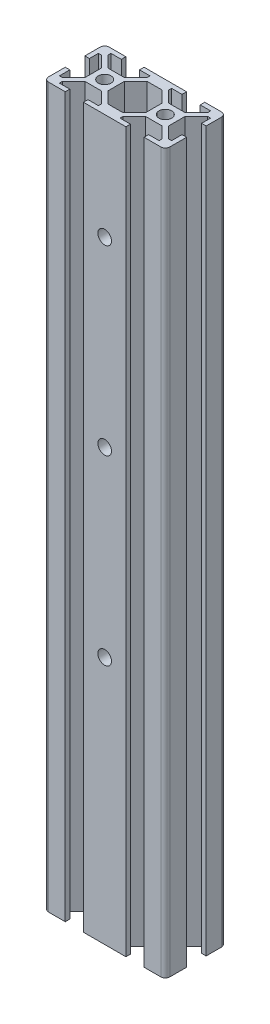
SolidWorks part; units mm, degrees
material "6063-O, Extruded Rod (SS)"
ref_plane "Front Plane" through (0, 0, 0) normal (0, 0, 1) x (1, 0, 0)
ref_plane "Top Plane" through (0, 0, 0) normal (0, 1, 0) x (1, 0, 0)
ref_plane "Right Plane" through (0, 0, 0) normal (1, 0, 0) x (0, 0, -1)
sketch "Sketch1" plane through (0, 0, 0) normal (0, 1, 0) x (1, 0, 0)
  line L0 (0, 0) -> (7, 0)
  line L1 (0, 0) -> (40, 0) construction
  line L2 (0, 0) -> (0, 20) construction
  line L3 (0, 20) -> (40, 20) construction
  line L4 (40, 0) -> (40, 20) construction
  line L5 (7, 0) -> (7, 1.5)
  line L6 (7, 1.5) -> (3.5607, 1.5)
  line L7 (3.5607, 1.5) -> (3.5607, 2.5)
  line L8 (3.5607, 2.5) -> (7.2607, 6.2)
  line L9 (12.7393, 6.2) -> (16.4393, 2.5)
  line L10 (16.4393, 2.5) -> (16.4393, 1.5)
  line L11 (13, 1.5) -> (13, 0)
  line L12 (13, 0) -> (27, 0)
  line L13 (27, 0) -> (27, 1.5)
  line L14 (27, 1.5) -> (23.5607, 1.5)
  line L15 (23.5607, 1.5) -> (23.5607, 2.5)
  line L16 (23.5607, 2.5) -> (27.2607, 6.2)
  line L17 (36.4393, 2.5) -> (36.4393, 1.5)
  line L18 (36.4393, 1.5) -> (33, 1.5)
  line L19 (33, 1.5) -> (33, 0)
  line L20 (33, 0) -> (40, 0)
  line L21 (40, 0) -> (40, 7)
  line L22 (40, 7) -> (38.5, 7)
  line L23 (38.5, 7) -> (38.5, 3.5607)
  line L24 (38.5, 3.5607) -> (37.5, 3.5607)
  line L25 (37.5, 3.5607) -> (33.8, 7.2607)
  line L26 (33.8, 7.2607) -> (33.8, 12.7393)
  line L27 (33.8, 12.7393) -> (37.5, 16.4393)
  line L28 (37.5, 16.4393) -> (38.5, 16.4393)
  line L29 (38.5, 16.4393) -> (38.5, 13.4532)
  line L30 (38.5, 13.4532) -> (40, 13.4532)
  line L31 (40, 13.4532) -> (40, 20)
  line L32 (40, 20) -> (33, 20)
  line L33 (33, 20) -> (33, 18.5)
  line L34 (33, 18.5) -> (36.4393, 18.5)
  line L35 (36.4393, 18.5) -> (36.4393, 17.5)
  line L36 (36.4393, 17.5) -> (32.7393, 13.8)
  line L37 (32.7393, 13.8) -> (27.2607, 13.8)
  line L38 (27.2607, 13.8) -> (23.5607, 17.5)
  line L39 (23.5607, 17.5) -> (23.5607, 18.5)
  line L40 (23.5607, 18.5) -> (27, 18.5)
  line L41 (27, 18.5) -> (27, 20)
  line L42 (27, 20) -> (13, 20)
  line L43 (13, 20) -> (13, 18.5)
  line L44 (13, 18.5) -> (16.4393, 18.5)
  line L45 (16.4393, 18.5) -> (16.4393, 17.5)
  line L46 (16.4393, 17.5) -> (12.7393, 13.8)
  line L47 (12.7393, 13.8) -> (7.2607, 13.8)
  line L48 (7.2607, 13.8) -> (3.5607, 17.5)
  line L49 (3.5607, 17.5) -> (3.5607, 18.5)
  line L50 (3.5607, 18.5) -> (7, 18.5)
  line L51 (7, 18.5) -> (7, 20)
  line L52 (7, 20) -> (0, 20)
  line L53 (0, 20) -> (0, 13.4532)
  line L54 (0, 13.4532) -> (1.5, 13.4532)
  line L55 (1.5, 13.4532) -> (1.5, 16.4393)
  line L56 (7.2607, 6.2) -> (12.7393, 6.2)
  line L57 (27.2607, 6.2) -> (32.7393, 6.2)
  line L58 (16.4393, 1.5) -> (13, 1.5)
  line L59 (32.7393, 6.2) -> (36.4393, 2.5)
  line L60 (40, 10) -> (-12.444, 10) construction
  line L61 (20, -12.9166) -> (20, 20) construction
  line L62 (1.5, 16.4393) -> (2.5, 16.4393)
  line L63 (2.5, 16.4393) -> (6.2, 12.7393)
  line L64 (6.2, 12.7393) -> (6.2, 7.2607)
  line L65 (6.2, 7.2607) -> (2.5, 3.5607)
  line L66 (2.5, 3.5607) -> (1.5, 3.5607)
  line L67 (1.5, 3.5607) -> (1.5, 7)
  line L68 (1.5, 7) -> (0, 7)
  line L69 (0, 7) -> (0, 0)
  line L70 (17.497, 16.4583) -> (13.778, 12.7393)
  line L71 (13.778, 12.7393) -> (13.778, 7.2607)
  line L72 (13.778, 7.2607) -> (17.497, 3.5417)
  line L73 (17.497, 3.5417) -> (22.503, 3.5417)
  line L74 (22.503, 3.5417) -> (26.222, 7.2607)
  line L75 (26.222, 7.2607) -> (26.222, 12.7393)
  line L76 (26.222, 12.7393) -> (22.503, 16.4583)
  line L77 (22.503, 16.4583) -> (17.497, 16.4583)
  circle A0 centre (10, 10) radius 2.1
  circle A1 centre (30, 10) radius 2.1
  point P22 (33.8, 10)
  point P34 (30, 6.2)
  point P66 (10, 6.2)
  point P79 (20, 3.5417)
  point P85 (13.778, 10)
  dimension "D6" = 4.2
  dimension "D1" = 40
  dimension "D2" = 20
  dimension "D3" = 6
  dimension "D4" = 1.5
  dimension "D5" = 6.2
  dimension "D7" = 20
  dimension "D8" = 1.5
  dimension "D9" = 1
  dimension "D10" = 45
extrude "Boss-Extrude1" add sketch "Sketch1" along normal blind 237
fillet "Fillet1" radius 1.5 4 edges at (0, 118.5, 0) (0, 118.5, -20) (40, 118.5, 0) (40, 118.5, -20)
hole_wizard "M4 Clearance Hole1" positions "Sketch3" profile "Sketch4" hole size "M4" standard "ISO" end condition through all
sketch "Sketch3" plane through (0, 0, 0) normal (0, 0, 1) x (1, 0, 0)
  line L0 (20, 237) -> (20, 0) construction
  line L1 (13, 237) -> (27, 237) construction
  line L2 (13, 0) -> (27, 0) construction
  point P0 (20, 202)
  point P27 (20, 142)
  point P28 (20, 82)
  dimension "D1" = 35
  dimension "D2" = 3
sketch "Sketch4" plane through (20, 202, 0) normal (1, 0, 0) x (0, -1, 0)
  line L0 (0, 0) -> (0, 20)
  line L1 (0, 20) -> (2.25, 20)
  line L2 (2.25, 20) -> (2.25, 0)
  line L5 (2.25, 0) -> (0, 0)
  line L11 (0, -6.35) -> (0, 107.95) construction
  dimension "Thru Hole Dia." = 4.5
  dimension "Thru Hole Depth" = 20
